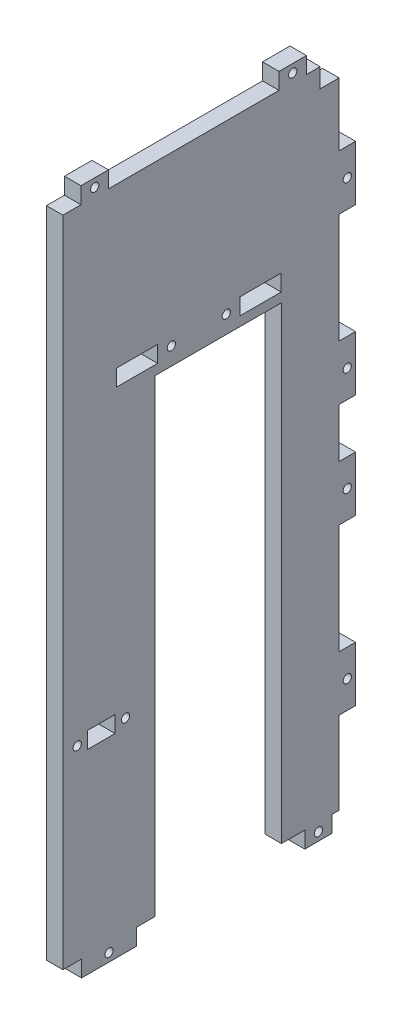
SolidWorks part; units mm, degrees
ref_plane "Plan de face" through (0, 0, 0) normal (0, 0, 1) x (1, 0, 0)
ref_plane "Plan de dessus" through (0, 0, 0) normal (0, 1, 0) x (1, 0, 0)
ref_plane "Plan de droite" through (0, 0, 0) normal (1, 0, 0) x (0, 0, -1)
sketch "Esquisse1" plane through (0, 0, 0) normal (1, 0, 0) x (0, 0, -1)
  line L0 (97.1531, 0) -> (-102.2664, 0) construction
  line L1 (-50.29, 119) -> (50.29, 119)
  line L2 (-50.29, 119) -> (-50.29, -119)
  line L3 (-50.29, -119) -> (50.29, -119)
  line L4 (50.29, 119) -> (50.29, -119)
  line L5 (0, 172.7153) -> (0, -236.1933) construction
  line L7 (-41.29, -48) -> (-31.29, -48)
  line L8 (-41.29, -48) -> (-41.29, -54)
  line L9 (-41.29, -54) -> (-31.29, -54)
  line L10 (-31.29, -48) -> (-31.29, -54)
  line L15 (-30.795, 61) -> (-15.795, 61)
  line L16 (-30.795, 61) -> (-30.795, 55)
  line L17 (-30.795, 55) -> (-15.795, 55)
  line L18 (-15.795, 61) -> (-15.795, 55)
  line L19 (14.205, 61) -> (29.205, 61)
  line L20 (14.205, 61) -> (14.205, 55)
  line L21 (14.205, 55) -> (29.205, 55)
  line L22 (29.205, 61) -> (29.205, 55)
  dimension "D1" = 238
  dimension "D2" = 100.58
  dimension "D4" = 119
  dimension "D13" = 15
  dimension "D14" = 15
  dimension "D15" = 30
  dimension "D16" = 6
  dimension "D17" = 6
  dimension "D3" = 50.29
  dimension "D6" = 19.495
  dimension "D7" = 9
  dimension "D8" = 167
  dimension "D9" = 6
  dimension "D10" = 10
extrude "Boss.-Extru.1" add sketch "Esquisse1" along normal blind 6
sketch "Esquisse3" plane through (6, 0, 0) normal (1, 0, 0) x (0, 0, -1)
  line L0 (-50.29, -119) -> (50.29, -119) construction
  line L1 (-43.5, -119) -> (-23.5, -119)
  line L2 (-43.5, -119) -> (-43.5, -125)
  line L3 (-43.5, -125) -> (-23.5, -125)
  line L4 (-23.5, -119) -> (-23.5, -125)
  line L5 (245.3741, 0) -> (-166.5298, 0) construction
  line L6 (50.29, -119) -> (50.29, 119) construction
  line L7 (37.79, -119) -> (47.79, -119)
  line L8 (37.79, -119) -> (37.79, -125)
  line L9 (37.79, -125) -> (47.79, -125)
  line L10 (0, 208.6671) -> (0, -232.3841) construction
  line L12 (47.79, -119) -> (47.79, -125)
  line L13 (56.29, 29) -> (56.29, 9)
  line L14 (50.29, 9) -> (56.29, 9)
  line L15 (50.29, 29) -> (50.29, 9)
  line L16 (50.29, 29) -> (56.29, 29)
  line L17 (56.29, 89) -> (56.29, 69)
  line L18 (50.29, 69) -> (56.29, 69)
  line L19 (50.29, 89) -> (50.29, 69)
  line L20 (50.29, 89) -> (56.29, 89)
  line L21 (50.29, 119) -> (-50.29, 119) construction
  line L22 (50.29, -89) -> (56.29, -89)
  line L23 (50.29, -89) -> (50.29, -69)
  line L24 (50.29, -69) -> (56.29, -69)
  line L25 (56.29, -89) -> (56.29, -69)
  line L26 (50.29, -29) -> (56.29, -29)
  line L27 (50.29, -29) -> (50.29, -9)
  line L28 (50.29, -9) -> (56.29, -9)
  line L29 (0, -208.6671) -> (0, 232.3841) construction
  line L30 (-50.29, 119) -> (-50.29, -119) construction
  line L34 (50.29, -119) -> (50.29, 119) construction
  line L35 (56.29, -29) -> (56.29, -9)
  line L36 (38.41, 119) -> (28.41, 119)
  line L37 (38.41, 119) -> (38.41, 125)
  line L38 (38.41, 125) -> (28.41, 125)
  line L39 (28.41, 119) -> (28.41, 125)
  line L40 (-50.29, 119) -> (-50.29, -119) construction
  line L41 (-33.71, 119) -> (-43.71, 119)
  line L42 (-33.71, 119) -> (-33.71, 125)
  line L43 (-33.71, 125) -> (-43.71, 125)
  line L44 (-43.71, 119) -> (-43.71, 125)
  dimension "D2" = 20
  dimension "D3" = 6
  dimension "D4" = 10
  dimension "D5" = 6.79
  dimension "D6" = 6
  dimension "D7" = 6
  dimension "D8" = 20
  dimension "D9" = 6
  dimension "D10" = 20
  dimension "D11" = 2.5
  dimension "D14" = 30
  dimension "D15" = 40
  dimension "D16" = 6
  dimension "D17" = 10
  dimension "D18" = 11.88
  dimension "D19" = 6.58
  dimension "D20" = 10
  dimension "D21" = 6
extrude "Boss.-Extru.5" add sketch "Esquisse3" against normal blind 6
sketch "Esquisse6" plane through (6, 0, 0) normal (1, 0, 0) x (0, 0, -1)
  line L0 (-23.5, -119) -> (37.79, -119) construction
  line L1 (-16.71, -119) -> (29.29, -119)
  line L2 (-16.71, -119) -> (-16.71, 51.59)
  line L3 (-16.71, 51.59) -> (29.29, 51.59)
  line L4 (29.29, -119) -> (29.29, 51.59)
  line L5 (50.29, -69) -> (50.29, -29) construction
  line L8 (28.41, 119) -> (-33.71, 119) construction
  dimension "D1" = 46
  dimension "D2" = 67.41
  dimension "D3" = 21
extrude "Enlèv. mat.-Extru.2" cut sketch "Esquisse6" against normal blind 6
sketch "Esquisse7" plane through (0, 0, 0) normal (-1, 0, 0) x (0, 0, 1)
  line L1 (-50.29, 119) -> (-43.41, 119)
  line L2 (-50.29, 119) -> (-50.29, 112)
  line L3 (-50.29, 112) -> (-43.41, 112)
  line L4 (-43.41, 119) -> (-43.41, 112)
  dimension "D1" = 7
  dimension "D2" = 6.88
extrude "Enlèv. mat.-Extru.3" cut sketch "Esquisse7" against normal blind 6
sketch "Esquisse8" plane through (0, 0, 0) normal (-1, 0, 0) x (0, 0, 1)
  line L0 (-51.0214, 58) -> (44.3386, 58) construction
  line L1 (43.5, -125) -> (23.5, -125) construction
  line L2 (-14.205, 61) -> (-14.205, 55) construction
  line L3 (15.795, 55) -> (15.795, 61) construction
  line L5 (60.5401, -51) -> (10.4957, -51) construction
  line L6 (41.29, -48) -> (41.29, -54) construction
  line L7 (31.29, -54) -> (31.29, -48) construction
  line L8 (41.29, -54) -> (31.29, -54) construction
  line L9 (53.2872, 122) -> (-67.0711, 122) construction
  line L10 (33.71, 125) -> (43.71, 125) construction
  line L11 (-28.41, 125) -> (-28.41, 119) construction
  line L12 (33.71, 119) -> (33.71, 125) construction
  line L13 (-67.0711, -122) -> (72.8873, -122) construction
  line L16 (-37.79, -119) -> (-37.79, -125) construction
  line L17 (23.5, -125) -> (23.5, -119) construction
  line L18 (-53.29, 135.0788) -> (-53.29, -173.0788) construction
  line L19 (-56.29, 69) -> (-56.29, 89) construction
  line L21 (-56.29, -69) -> (-50.29, -69) construction
  line L22 (-50.29, 9) -> (-56.29, 9) construction
  line L23 (-56.29, 89) -> (-50.29, 89) construction
  circle A1 centre (-9.205, 58) radius 1.5
  circle A2 centre (10.795, 58) radius 1.5
  circle A4 centre (27.5, -51) radius 1.5
  circle A5 centre (45.08, -51) radius 1.5
  circle A6 centre (38.71, 122) radius 1.5
  circle A7 centre (-33.41, 122) radius 1.5
  circle A8 centre (33.5, -122) radius 1.5
  circle A9 centre (-53.29, 79) radius 1.5
  circle A10 centre (-42.79, -122) radius 1.5
  circle A11 centre (-53.29, 19) radius 1.5
  circle A12 centre (-53.29, -79) radius 1.5
  circle A13 centre (-53.29, -19) radius 1.5
  dimension "D1" = 3
  dimension "D2" = 3
  dimension "D4" = 3
  dimension "D6" = 5
  dimension "D7" = 5
  dimension "D9" = 3
  dimension "D10" = 3
  dimension "D15" = 3
  dimension "D16" = 3
  dimension "D17" = 5
  dimension "D18" = 5
  dimension "D20" = 3
  dimension "D21" = 3
  dimension "D22" = 3
  dimension "D23" = 3
  dimension "D24" = 5
  dimension "D25" = 10
  dimension "D26" = 3
  dimension "D27" = 3
  dimension "D28" = 3
  dimension "D29" = 10
  dimension "D31" = 10
  dimension "D32" = 10
  dimension "D11" = 3.79
  dimension "D12" = 3.79
  dimension "D13" = 3
  dimension "D14" = 3
  dimension "D30" = 10
extrude "Enlèv. mat.-Extru.4" cut sketch "Esquisse8" against normal blind 6
equation "\"D3@Esquisse1\"=\"D2@Esquisse1\"/2"
equation "\"D4@Esquisse1\"=\"D1@Esquisse1\"/2"
